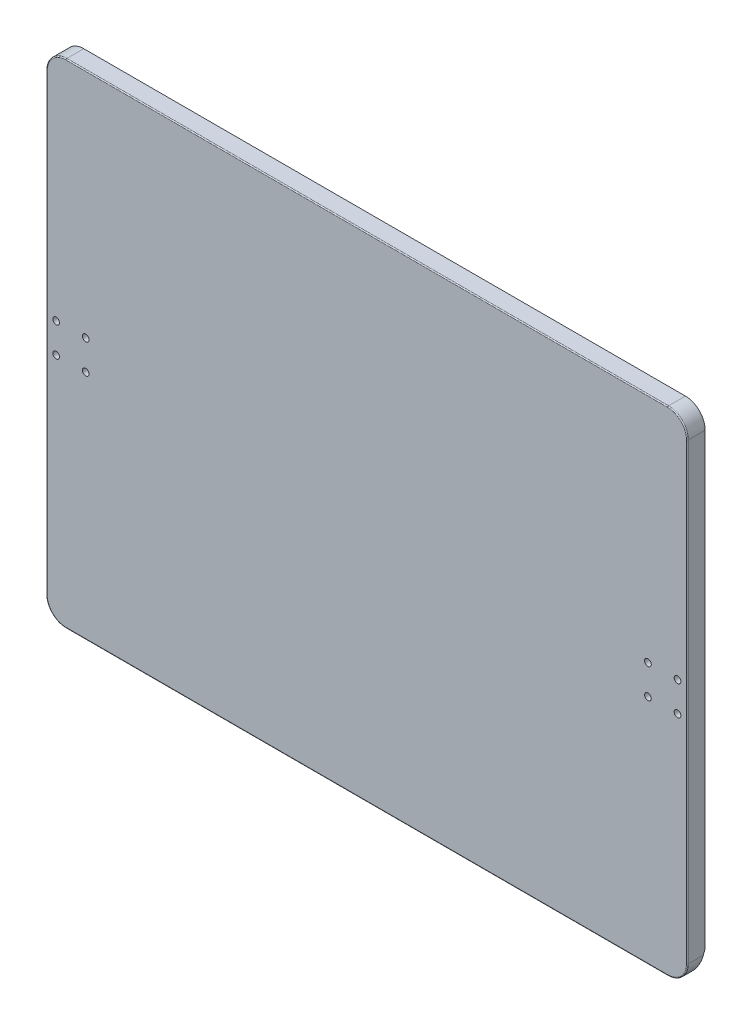
SolidWorks part; units mm, degrees
material "Beech"
ref_plane "Front Plane" through (0, 0, 0) normal (0, 0, 1) x (1, 0, 0)
ref_plane "Top Plane" through (0, 0, 0) normal (0, 1, 0) x (1, 0, 0)
ref_plane "Right Plane" through (0, 0, 0) normal (1, 0, 0) x (0, 0, -1)
sketch "Sketch1" plane through (0, 0, 0) normal (0, 0, 1) x (1, 0, 0)
  line L1 (0, 0) -> (650, 0)
  line L2 (0, 0) -> (0, 500)
  line L3 (0, 500) -> (650, 500)
  line L4 (650, 0) -> (650, 500)
  dimension "D1" = 500
  dimension "D2" = 650
extrude "base" add sketch "Sketch1" along normal blind 18
hole_wizard "counterbored M5 bolt holes" positions "Sketch2" profile "Sketch3" hole size "1/4" standard "ANSI Inch" end condition through all
sketch "Sketch2" plane through (0, 0, 18) normal (0, 0, 1) x (1, 0, 0)
  line L1 (10, 265) -> (40, 265)
  line L2 (10, 265) -> (10, 235)
  line L3 (10, 235) -> (40, 235)
  line L4 (40, 265) -> (40, 235)
  line L5 (10, 250) -> (0, 250)
  line L6 (0, 500) -> (0, 0) construction
  point P1 (10, 265)
  point P2 (40, 235)
  point P41 (10, 235)
  point P42 (40, 265)
  dimension "D1" = 30
  dimension "D2" = 30
  dimension "D3" = 10
sketch "Sketch3" plane through (10, 265, 18) normal (1, 0, 0) x (0, -1, 0)
  line L0 (0, 0) -> (0, 18)
  line L1 (0, 18) -> (3.3782, 18)
  line L2 (3.3782, 18) -> (3.3782, 0)
  line L5 (3.3782, 0) -> (0, 0)
  line L11 (0, -6.35) -> (0, 107.95) construction
  dimension "Thru Hole Dia." = 6.7564
  dimension "Thru Hole Depth" = 18
ref_plane "midplane in x" through (325, 0, 0) normal (-1, 0, 0) x (0, 0, 1)
mirror "mirror counterbored bolt holes" about plane through (325, 0, 0) normal (-1, 0, 0) of "counterbored M5 bolt holes"
fillet "round corners" radius 20 4 edges at (0, 500, 9) (650, 500, 9) (650, 0, 9) (0, 0, 9)
fillet "break top edge" radius 1 8 edges at (5.8579, 494.1421, 18) (325, 500, 18) (644.1421, 494.1421, 18) (650, 250, 18) (644.1421, 5.8579, 18) (325, 0, 18) (5.8579, 5.8579, 18) (0, 250, 18)
chamfer "front shadow chamfer" distance 25 angle 20 1 edges at (325, 0, 0) tangent propagation no first distance on face at (643.3782, 265, 0)
fillet "round chamfer edges" [suppressed] radius 1
equation "\"board_thickness\"= 18mm"
equation "\"way_width\"= 75mm"
equation "\"way_thickness\"= 50mm"
equation "\"radial_clearance\"= 0.1mm"
equation "\"slider_width\"= \"way_width\"-2* \"radial_clearance\""
equation "\"slider_thickness\"= \"way_thickness\" - 2 * \"radial_clearance\""
equation "\"column_width\"= \"way_width\" + 2 * \"board_thickness\""
equation "\"boxway_slot_width\"= 50mm"
equation "\"keeper_rail_width\"= (\"column_width\" - \"boxway_slot_width\")/2"
equation "\"slider_length\"= 125mm"
equation "\"nut_diameter\"= 22mm"
equation "\"nut_length\"= 15mm"
equation "\"leadscrew_diameter\"= 10mm"
equation "\"leadscrew_radial_clearance\"= 1mm"
equation "\"bearing_bolt_pattern_width\"= 30mm"
equation "\"bearing_bolt_pattern_height\"= 75mm"
equation "\"desktop_bolt_pattern_width\"= 30mm"
equation "\"desktop_bolt_pattern_height\"= 30mm"
equation "\"bearing_bolt_nut_counterbore_diameter\"= 12mm"
equation "\"bearing_bolt_nut_counterbore_depth\"= 10mm"
equation "\"desktop_depth\"= 500mm"
equation "\"desktop_width\"= 650mm"
equation "\"D1@Sketch1\"=\"desktop_depth\""
equation "\"D2@Sketch1\"=\"desktop_width\""
equation "\"desktop_thickness\"= 18mm"
equation "\"D1@base\" = \"desktop_thickness\""
equation "\"D1@Sketch2\"=\"desktop_bolt_pattern_height\""
equation "\"D2@Sketch2\"=\"desktop_bolt_pattern_width\""
